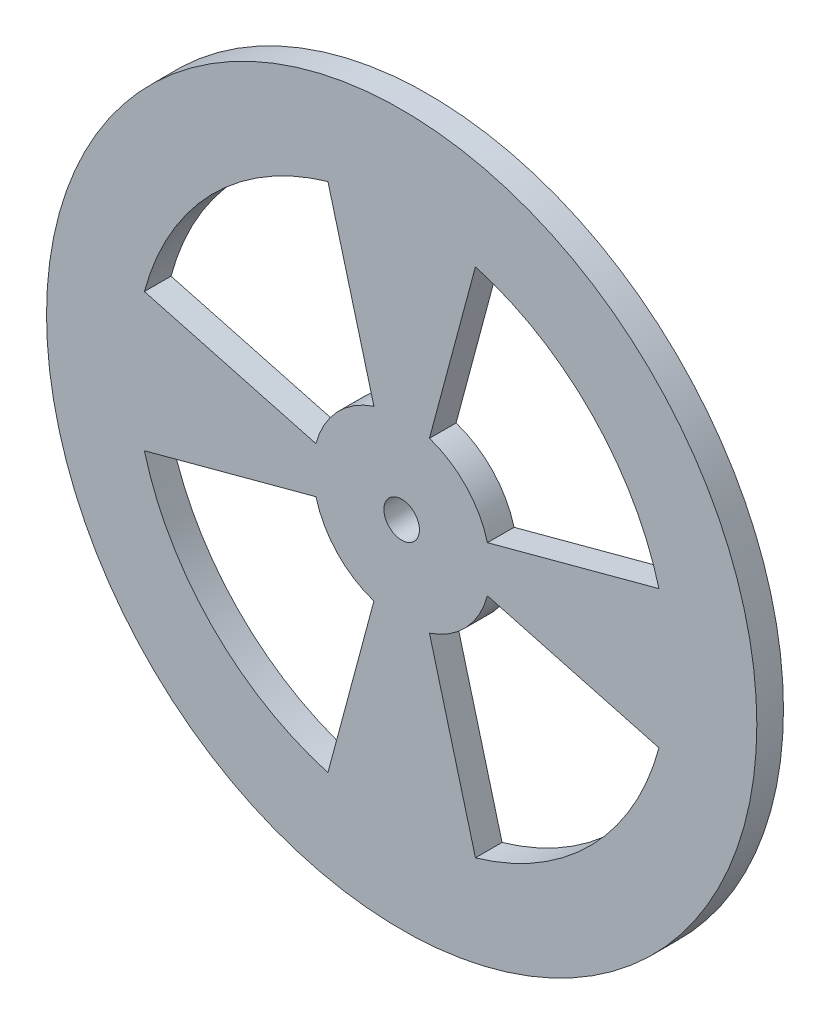
SolidWorks part; units mm, degrees
ref_plane "Plan de face" through (0, 0, 0) normal (0, 0, 1) x (1, 0, 0)
ref_plane "Plan de dessus" through (0, 0, 0) normal (0, 1, 0) x (1, 0, 0)
ref_plane "Plan de droite" through (0, 0, 0) normal (1, 0, 0) x (0, 0, -1)
sketch "Esquisse1" plane through (0, 0, 0) normal (0, 0, 1) x (1, 0, 0)
  line L0 (0, 0) -> (-29.4323, 0) construction
  line L1 (0, 0) -> (0, 24.3094) construction
  line L2 (-8.3068, 28.827) -> (-3.1277, 9.4983)
  line L3 (-9.6593, 2.5882) -> (-28.9778, 7.7646)
  line L4 (-8.3068, -28.827) -> (-3.1277, -9.4983)
  line L5 (-9.6593, -2.5882) -> (-28.9778, -7.7646)
  line L6 (8.3068, 28.827) -> (3.1277, 9.4983)
  line L7 (9.6593, 2.5882) -> (28.9778, 7.7646)
  line L8 (9.6593, -2.5882) -> (28.9778, -7.7646)
  line L9 (8.3068, -28.827) -> (3.1277, -9.4983)
  circle A0 centre (0, 0) radius 40
  circle A1 centre (0, 0) radius 2
  circle A2 centre (0, 0) radius 30
  circle A3 centre (0, 0) radius 10
  dimension "D1" = 80
  dimension "D2" = 4
  dimension "D3" = 10
  dimension "D6" = 20
  dimension "D4" = 15
  dimension "D5" = 15
extrude "Boss.-Extru.1" add sketch "Esquisse1" along normal blind 3 contours A3 L6 A2 L2 | A3 A1 | A3 L8 A2 L7 | A3 L4 A2 L9 | A0 A2 | A3 L3 A2 L5 region at (0, 21.2086, 0) region at (0, 9.7172, 0) region at (-21.42, 0, 0) region at (21.42, 0, 0) region at (0, -21.2086, 0) region at (-38.8686, 0, 0)
